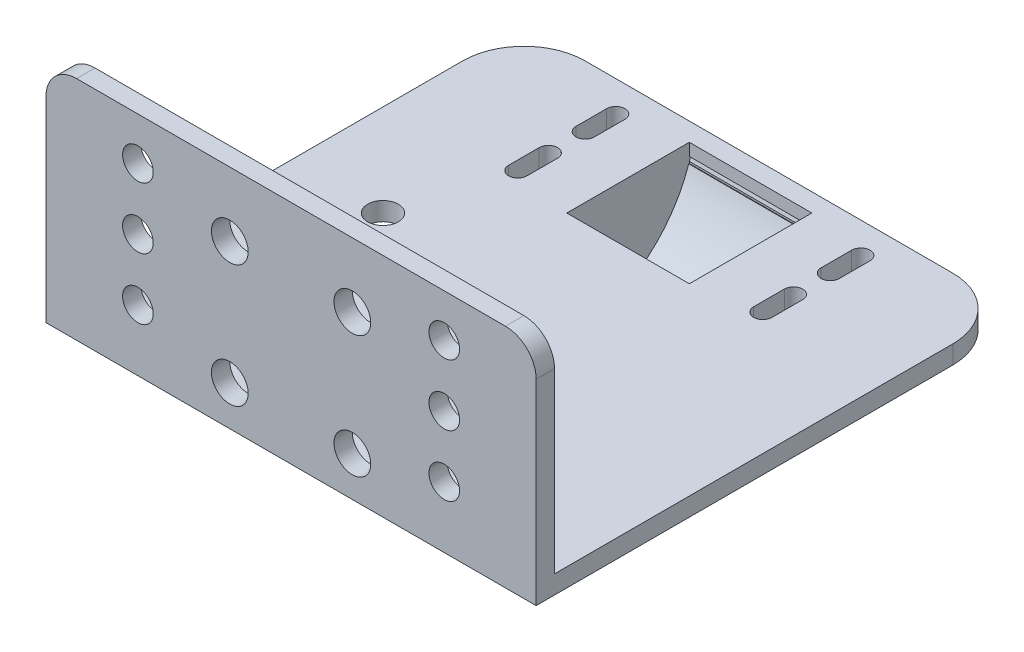
SolidWorks part; units mm, degrees
ref_plane "Płaszczyzna przednia" through (0, 0, 0) normal (0, 0, 1) x (1, 0, 0)
ref_plane "Płaszczyzna górna" through (0, 0, 0) normal (0, 1, 0) x (1, 0, 0)
ref_plane "Płaszczyzna prawa" through (0, 0, 0) normal (1, 0, 0) x (0, 0, -1)
sketch "Szkic2" plane through (0, 0, 0) normal (0, 0, 1) x (1, 0, 0)
  line L0 (0, 18.5) -> (0, -18.5) construction
  line L1 (-40, -18.5) -> (40, -18.5)
  line L2 (-40, -18.5) -> (-40, 18.5)
  line L3 (-40, 18.5) -> (40, 18.5)
  line L4 (40, -18.5) -> (40, 18.5)
  line L5 (-40, -18.5) -> (40, 18.5) construction
  line L6 (-40, 18.5) -> (40, -18.5) construction
  line L7 (-40, 0) -> (40, 0) construction
  circle A0 centre (-10, -12) radius 3
  circle A1 centre (-25, -8.5) radius 2.5
  circle A2 centre (-25, 1.5) radius 2.5
  circle A3 centre (-25, 11.5) radius 2.5
  circle A5 centre (10, -12) radius 3
  circle A6 centre (25, -8.5) radius 2.5
  circle A7 centre (25, 1.5) radius 2.5
  circle A9 centre (25, 11.5) radius 2.5
  circle A10 centre (-10, 8) radius 3
  circle A12 centre (10, 8) radius 3
  point P0 (0, 0)
  dimension "D3" = 6
  dimension "D6" = 5
  dimension "D10" = 6
  dimension "D1" = 80
  dimension "D2" = 37
  dimension "D4" = 6.5
  dimension "D5" = 10
  dimension "D7" = 10
  dimension "D8" = 15
  dimension "D11" = 20
  dimension "D12" = 10
  dimension "D9" = 3
extrude "Dodanie-wyciągnięcie1" add sketch "Szkic2" along normal blind 3
fillet "Zaokrąglenie1" radius 5 2 edges at (40, 18.5, 1.5) (-40, 18.5, 1.5)
sketch "Szkic3" plane through (0, 0, 0) normal (0, 0, -1) x (-1, 0, 0)
  line L0 (40, 13.5) -> (40, -18.5) construction
  line L1 (-40, -18.5) -> (40, -18.5)
  line L2 (-40, -18.5) -> (-40, -15.5)
  line L3 (-40, -15.5) -> (40, -15.5)
  line L4 (40, -18.5) -> (40, -15.5)
  dimension "D1" = 3
extrude "Dodanie-wyciągnięcie2" add sketch "Szkic3" along normal blind 75
sketch "Szkic4" plane through (0, -18.5, 0) normal (0, -1, 0) x (1, 0, 0)
  line L0 (0, 3) -> (0, -75) construction
  line L1 (-40, 3) -> (40, 3) construction
  line L2 (40, -75) -> (-40, -75) construction
  line L3 (10, -52) -> (-10, -52)
  line L4 (-10, -52) -> (-10, -72)
  line L5 (-10, -72) -> (10, -72)
  line L6 (10, -72) -> (10, -52)
  line L7 (-21.5, -70) -> (-21.5, -65)
  line L8 (-18.5, -70) -> (-18.5, -65)
  line L9 (-10, -62) -> (10, -62) construction
  line L10 (-18.5, -54) -> (-18.5, -59)
  line L11 (-21.5, -54) -> (-21.5, -59)
  line L12 (21.5, -54) -> (21.5, -59)
  line L13 (18.5, -54) -> (18.5, -59)
  line L14 (18.5, -70) -> (18.5, -65)
  line L15 (21.5, -70) -> (21.5, -65)
  circle A1 centre (-5.5, -7) radius 1.5
  circle A2 centre (-20, -70) radius 1.5
  circle A3 centre (-20, -65) radius 1.5
  circle A4 centre (-20, -59) radius 1.5
  circle A5 centre (-20, -54) radius 1.5
  circle A6 centre (20, -54) radius 1.5
  circle A7 centre (20, -59) radius 1.5
  circle A8 centre (20, -65) radius 1.5
  circle A9 centre (20, -70) radius 1.5
  point P14 (0, -52)
  dimension "D1" = 3
  dimension "D7" = 3
  dimension "D10" = 3
  dimension "D12" = 10
  dimension "D2" = 20
  dimension "D3" = 5.5
  dimension "D4" = 7
  dimension "D5" = 20
  dimension "D6" = 45
  dimension "D8" = 10
  dimension "D9" = 5
  dimension "D11" = 5
  dimension "D13" = 3
extrude "Wytnij-wyciągnięcie1" cut sketch "Szkic4" against normal up to next contours A4 | L10 A5 L11 A4 | A3 | A3 L7 A2 L8 | A2 | A6 | A7 L12 A6 L13 | A7 | A8 | L14 A9 L15 A8 | A9 | A5 region at (-20, -18.5, -67.5) region at (-20, -18.5, -70) region at (-20, -18.5, -65) region at (-20, -18.5, -54) region at (-20, -18.5, -56.5) region at (-20, -18.5, -59) region at (20, -18.5, -54) region at (20, -18.5, -56.5) region at (20, -18.5, -59) region at (20, -18.5, -67.5) region at (20, -18.5, -70) region at (20, -18.5, -65)
ref_plane "Płaszczyzna1" through (12, 0, 0) normal (1, 0, 0) x (0, 0, -1)
sketch "Szkic8" plane through (12, 0, 0) normal (1, 0, 0) x (0, 0, -1)
  line L0 (50, -18.5) -> (50, -35.5)
  line L3 (50, -18.5) -> (74, -18.5)
  arc A0 (74, -18.5) -> (50, -35.5) centre (51.0367, -11.5224) cw
  dimension "D5" = 24
  dimension "D1" = 17
  dimension "D2" = 25
  dimension "D3" = 0
  dimension "D4" = 24
extrude "Dodanie-wyciągnięcie3" add sketch "Szkic8" against normal blind 24
shell "Skorupa8" thickness 2 removed face at (0, -27, -50)
sketch "Szkic10" plane through (0, -15.5, 0) normal (0, 1, 0) x (1, 0, 0)
  line L0 (0, 75) -> (0, 0) construction
  line L1 (-40, 75) -> (40, 75) construction
  line L2 (35, 0) -> (-35, 0) construction
  line L4 (10, 52) -> (-10, 52)
  line L5 (10, 52) -> (10, 72)
  line L6 (10, 72) -> (-10, 72)
  line L7 (-10, 52) -> (-10, 72)
  line L8 (10, 52) -> (-10, 72) construction
  line L9 (10, 72) -> (-10, 52) construction
  point P6 (0, 62)
  dimension "D1" = 20
  dimension "D2" = 20
  dimension "D3" = 3
extrude "Wytnij-wyciągnięcie5" cut sketch "Szkic10" against normal blind 3
extrude "Wytnij-wyciągnięcie7" cut sketch "Szkic4<5>" against normal blind 3 contours A1 region at (-5.5, -18.5, -7)
sketch "Szkic4<5>" plane through (0, -18.5, 0) normal (0, -1, 0) x (1, 0, 0) same geometry as "Szkic4"
fillet "Zaokrąglenie2" radius 10 2 edges at (40, -17, -75) (-40, -17, -75)
sketch "Szkic11" plane through (0, -18.5, 0) normal (0, -1, 0) x (1, 0, 0)
  line L0 (-40, 3) -> (-40, -65) construction
  line L1 (-40, 3) -> (40, 3) construction
  circle A0 centre (-25, -7) radius 2.5
  circle A1 centre (-25, -17) radius 2.5
  circle A2 centre (-25, -27) radius 2.5
  circle A3 centre (-25, -37) radius 2.5
  dimension "D1" = 5
  dimension "D2" = 15
  dimension "D3" = 10
  dimension "D4" = 4
extrude "Wytnij-wyciągnięcie8" cut sketch "Szkic11" against normal up to next
